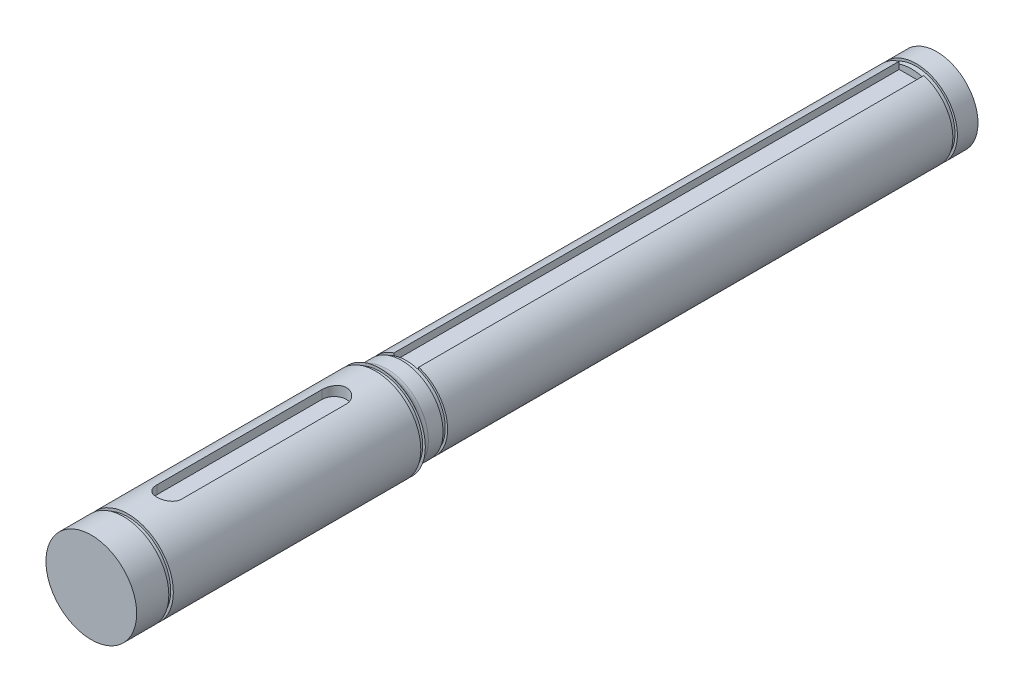
SolidWorks part; units mm, degrees
ref_plane "Front Plane" through (0, 0, 0) normal (0, 0, 1) x (1, 0, 0)
ref_plane "Top Plane" through (0, 0, 0) normal (0, 1, 0) x (1, 0, 0)
ref_plane "Right Plane" through (0, 0, 0) normal (1, 0, 0) x (0, 0, -1)
sketch "Sketch2" plane through (0, 0, 0) normal (0, 0, 1) x (1, 0, 0)
  circle A0 centre (0, 0) radius 10
extrude "Boss-Extrude1" add sketch "Sketch2" along normal blind 135
ref_plane "Plane1" through (0, 0, 5) normal (0, 0, -1) x (-1, 0, 0)
sketch "Sketch3" plane through (0, 0, 5) normal (0, 0, -1) x (-1, 0, 0)
  circle A0 centre (0, 0) radius 10
  circle A1 centre (0, 0) radius 9.43
  dimension "D1" = 18.86
extrude "Cut-Extrude2" cut sketch "Sketch3" against normal blind 1.1
ref_plane "Plane2" through (0, 0, 67.35) normal (0, 0, -1) x (-1, 0, 0)
mirror "Mirror1" about plane through (0, 0, 67.35) normal (0, 0, -1) of "Cut-Extrude2"
sketch "Sketch4" plane through (0, 0, 67.35) normal (0, 0, -1) x (-1, 0, 0)
  line L0 (0, -10) -> (0, 7.81) construction
  line L1 (-3, 7.81) -> (3, 7.81)
  line L2 (-3, 7.81) -> (-3, 10.8778)
  line L3 (-3, 10.8778) -> (3, 10.8778)
  line L4 (3, 10.8778) -> (3, 7.81)
  circle A0 centre (0, 0) radius 10 construction
  point P9 (0, 7.81)
  dimension "D1" = 17.81
  dimension "D2" = 6
extrude "Cut-Extrude3" cut sketch "Sketch4" against normal mid plane 122.5
ref_plane "Plane3" through (0, 0, 135) normal (0, 0, 1) x (1, 0, 0)
sketch "Sketch5" plane through (0, 0, 135) normal (0, 0, 1) x (1, 0, 0)
  circle A0 centre (0, 0) radius 11
extrude "Boss-Extrude2" add sketch "Sketch5" along normal blind 70
fillet "Fillet3" radius 2 1 edges at (10, 0, 135)
sketch "Sketch6" plane through (0, 0, 135) normal (0, 0, 1) x (1, 0, 0)
  circle A0 centre (0, 0) radius 11
  circle A1 centre (0, 0) radius 10.35
extrude "Cut-Extrude4" cut sketch "Sketch6" along normal blind 1.1
ref_plane "Plane4" through (0, 0, 166.1) normal (0, 0, 1) x (1, 0, 0)
mirror "Mirror2" about plane through (0, 0, 166.1) normal (0, 0, 1) of "Cut-Extrude4"
ref_plane "Plane5" through (0, 11, 0) normal (0, 1, 0) x (1, 0, 0)
sketch "Sketch8" plane through (0, 11, 0) normal (0, 1, 0) x (1, 0, 0)
  line L0 (0, -136.1) -> (0, -146.1) construction
  line L1 (11, -136.1) -> (-11, -136.1) construction
  line L2 (0, -146.1) -> (0, -186.1) construction
  line L3 (3, -146.1) -> (3, -186.1)
  line L4 (-3, -146.1) -> (-3, -186.1)
  arc A0 (3, -146.1) -> (-3, -146.1) centre (0, -146.1) ccw
  arc A1 (-3, -186.1) -> (3, -186.1) centre (0, -186.1) ccw
  point P5 (0, -166.1)
  dimension "D1" = 10
  dimension "D2" = 40
  dimension "D3" = 6
extrude "Cut-Extrude5" cut sketch "Sketch8" against normal blind 2.5
